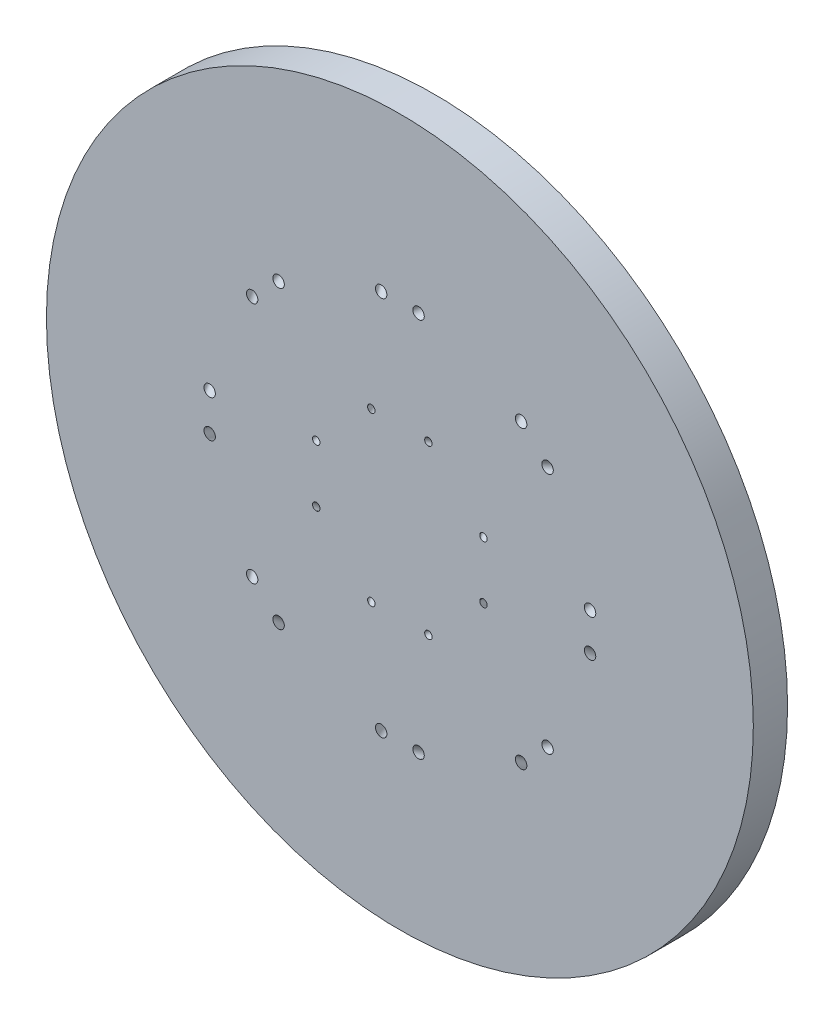
SolidWorks part; units mm, degrees
ref_plane "Front Plane" through (0, 0, 0) normal (0, 0, 1) x (1, 0, 0)
ref_plane "Top Plane" through (0, 0, 0) normal (0, 1, 0) x (1, 0, 0)
ref_plane "Right Plane" through (0, 0, 0) normal (1, 0, 0) x (0, 0, -1)
sketch "Sketch1" plane through (0, 0, 0) normal (0, 0, 1) x (1, 0, 0)
  circle A0 centre (0, 0) radius 38.1
  dimension "D1" = 76.2
extrude "Boss-Extrude1" add sketch "Sketch1" against normal blind 3.6912
sketch "Sketch2" plane through (0, 0, 0) normal (0, 0, 1) x (1, 0, 0)
  line L0 (0, 0) -> (0, 20.6) construction
  line L1 (0, 0) -> (20.6, 0) construction
  circle A0 centre (0, 0) radius 20.6 construction
  circle A1 centre (0, 0) radius 9.525 construction
  dimension "D1" = 41.2
  dimension "D2" = 19.05
sketch "Sketch4" plane through (0, 0, 0) normal (0, 0, 1) x (1, 0, 0)
  line L0 (-3.076, 9.0146) -> (3.076, 9.0146) construction
  line L1 (0, 0) -> (0, 20.6) construction
  line L3 (9.0146, 3.076) -> (9.0146, -3.076) construction
  line L4 (3.076, -9.0146) -> (-3.076, -9.0146) construction
  line L5 (-9.0146, -3.076) -> (-9.0146, 3.076) construction
  line L6 (-3.076, -9.0146) -> (3.076, -9.0146) construction
  line L8 (-9.0146, 3.076) -> (-9.0146, -3.076) construction
  circle A1 centre (9.0146, 3.076) radius 0.403
  circle A3 centre (-3.076, 9.0146) radius 0.403
  circle A4 centre (0, 0) radius 9.525 construction
  circle A5 centre (3.076, 9.0146) radius 0.403
  circle A6 centre (9.0146, -3.076) radius 0.403
  circle A7 centre (3.076, -9.0146) radius 0.403
  circle A8 centre (-3.076, -9.0146) radius 0.403
  circle A9 centre (-9.0146, -3.076) radius 0.403
  circle A10 centre (-9.0146, 3.076) radius 0.403
  point P6 (0, 9.0146)
  point P40 (0, 0)
  dimension "D1" = 0.806
  dimension "D2" = 0.806
  dimension "D3" = 6.152
  dimension "D4" = 4
sketch "Sketch5" plane through (0, 0, 0) normal (0, 0, 1) x (1, 0, 0)
  line L0 (-2.015, 20.5012) -> (2.015, 20.5012) construction
  line L1 (0, 0) -> (0, 20.6) construction
  line L2 (13.0717, 15.9214) -> (15.9214, 13.0717) construction
  line L3 (20.5012, -2.015) -> (20.5012, 2.015) construction
  line L4 (13.0717, -15.9214) -> (15.9214, -13.0717) construction
  line L5 (-2.015, -20.5012) -> (2.015, -20.5012) construction
  line L6 (-15.9214, -13.0717) -> (-13.0717, -15.9214) construction
  line L7 (-20.5012, 2.015) -> (-20.5012, -2.015) construction
  line L8 (-13.0717, 15.9214) -> (-15.9214, 13.0717) construction
  circle A0 centre (-2.015, 20.5012) radius 0.6152
  circle A1 centre (0, 0) radius 20.6 construction
  circle A2 centre (2.015, 20.5012) radius 0.6152
  circle A3 centre (13.0717, 15.9214) radius 0.6152
  circle A4 centre (15.9214, 13.0717) radius 0.6152
  circle A5 centre (20.5012, 2.015) radius 0.6152
  circle A6 centre (20.5012, -2.015) radius 0.6152
  circle A7 centre (15.9214, -13.0717) radius 0.6152
  circle A8 centre (13.0717, -15.9214) radius 0.6152
  circle A9 centre (2.015, -20.5012) radius 0.6152
  circle A10 centre (-2.015, -20.5012) radius 0.6152
  circle A11 centre (-13.0717, -15.9214) radius 0.6152
  circle A12 centre (-15.9214, -13.0717) radius 0.6152
  circle A13 centre (-20.5012, -2.015) radius 0.6152
  circle A14 centre (-20.5012, 2.015) radius 0.6152
  circle A15 centre (-15.9214, 13.0717) radius 0.6152
  circle A16 centre (-13.0717, 15.9214) radius 0.6152
  point P6 (0, 20.5012)
  point P28 (0, 0)
  dimension "D1" = 1.2304
  dimension "D2" = 1.2304
  dimension "D3" = 4.03
  dimension "D4" = 8
ref_plane "Plane1" through (0, 17.9868, 6.725) normal (0, 0.9367, 0.3502) x (1, 0, 0)
ref_plane "Plane2" through (0, 7.909, -2.9571) normal (0, -0.9367, 0.3502) x (1, 0, 0)
ref_plane "Plane3" through (12.7186, 12.7186, 6.725) normal (0.6623, 0.6623, 0.3502) x (0.7071, -0.7071, 0)
ref_plane "Plane4" through (17.9868, 0, 6.725) normal (0.9367, 0, 0.3502) x (0, 1, 0)
ref_plane "Plane5" through (12.7186, -12.7186, 6.725) normal (0.6623, -0.6623, 0.3502) x (0.7071, 0.7071, 0)
ref_plane "Plane7" through (-7.909, 0, -2.9571) normal (0.9367, 0, 0.3502) x (0, -1, 0)
ref_plane "Plane8" through (0, -7.909, -2.9571) normal (0, 0.9367, 0.3502) x (-1, 0, 0)
ref_plane "Plane9" through (0, -7.909, -2.9571) normal (0, 0.9367, 0.3502) x (1, 0, 0)
ref_plane "Plane10" through (-12.7186, -12.7186, 6.725) normal (-0.6623, -0.6623, 0.3502) x (0.7071, -0.7071, 0)
ref_plane "Plane11" through (-7.909, 0, 2.9571) normal (-0.9367, 0, 0.3502) x (0, 1, 0)
ref_plane "Plane12" through (7.909, 0, -2.9571) normal (-0.9367, 0, 0.3502) x (0, -1, 0)
ref_plane "Plane13" through (-12.7186, 12.7186, 6.725) normal (-0.6623, 0.6623, 0.3502) x (-0.7071, -0.7071, 0)
ref_plane "Plane14" through (0, -17.9868, 6.725) normal (0, -0.9367, 0.3502) x (1, 0, 0)
sketch "Sketch6" plane through (12.7186, -12.7186, 6.725) normal (0.6623, -0.6623, 0.3502) x (0.7071, 0.7071, 0)
  line L0 (-2.015, -7.1797) -> (2.015, -7.1797)
  line L1 (0, -7.1797) -> (0, -3.6896) construction
  line L2 (-2.015, -7.1797) -> (0, -3.6896)
  line L3 (0, -3.6896) -> (2.015, -7.1797)
  dimension "D1" = 60
sketch "Sketch7" plane through (17.9868, 0, 6.725) normal (0.9367, 0, 0.3502) x (0, 1, 0)
  line L0 (-2.015, -7.1797) -> (2.015, -7.1797)
  line L1 (0, -7.1797) -> (0, -3.6896) construction
  line L2 (-2.015, -7.1797) -> (0, -3.6896)
  line L3 (0, -3.6896) -> (2.015, -7.1797)
  dimension "D1" = 60
sketch "Sketch8" plane through (12.7186, 12.7186, 6.725) normal (0.6623, 0.6623, 0.3502) x (0.7071, -0.7071, 0)
  line L0 (-2.015, 7.1797) -> (2.015, 7.1797)
  line L1 (0, 7.1797) -> (0, 3.6896) construction
  line L3 (-2.015, 7.1797) -> (0, 3.6896)
  line L4 (0, 3.6896) -> (2.015, 7.1797)
  dimension "D1" = 60
sketch "Sketch9" plane through (0, 17.9868, 6.725) normal (0, 0.9367, 0.3502) x (1, 0, 0)
  line L0 (-2.015, 7.1797) -> (2.015, 7.1797)
  line L1 (0, 7.1797) -> (0, 3.6896) construction
  line L2 (0, 0) -> (0, 7.2143) construction
  line L3 (-2.015, 7.1797) -> (0, 3.6896)
  line L4 (0, 3.6896) -> (2.015, 7.1797)
  dimension "D1" = 60
sketch "Sketch10" plane through (0, 7.909, -2.9571) normal (0, -0.9367, 0.3502) x (1, 0, 0)
  line L0 (-3.076, 3.157) -> (3.076, 3.157)
  line L1 (0, 3.157) -> (0, 8.4848) construction
  line L2 (0, 0) -> (0, 7.2143) construction
  line L3 (0, 8.4848) -> (-3.076, 3.157)
  line L4 (0, 8.4848) -> (3.076, 3.157)
  dimension "D1" = 60
sketch "Sketch12" plane through (-7.909, 0, -2.9571) normal (0.9367, 0, 0.3502) x (0, -1, 0)
  line L0 (-3.076, -3.157) -> (3.076, -3.157)
  line L1 (0, -3.157) -> (0, -8.4848) construction
  line L2 (-3.076, -3.157) -> (0, -8.4848)
  line L3 (0, -8.4848) -> (3.076, -3.157)
  dimension "D1" = 60
sketch "Sketch14" plane through (0, -7.909, -2.9571) normal (0, 0.9367, 0.3502) x (1, 0, 0)
  line L0 (-3.076, -3.157) -> (3.076, -3.157)
  line L1 (0, -3.157) -> (0, -8.4848) construction
  line L2 (-3.076, -3.157) -> (0, -8.4848)
  line L3 (0, -8.4848) -> (3.076, -3.157)
  dimension "D1" = 60
ref_plane "Plane15" through (-17.9868, 0, 6.725) normal (-0.9367, 0, 0.3502) x (0, -1, 0)
sketch "Sketch16" plane through (7.909, 0, -2.9571) normal (-0.9367, 0, 0.3502) x (0, -1, 0)
  line L0 (-3.076, 3.157) -> (3.076, 3.157)
  line L4 (-3.076, 3.157) -> (0, 8.4848)
  line L5 (0, 8.4848) -> (3.076, 3.157)
  line L6 (0, 3.157) -> (0, 8.4848) construction
  dimension "D2" = 60
sketch "Sketch17" plane through (0, -7.909, -2.9571) normal (0, 0.9367, 0.3502) x (-1, 0, 0)
  line L0 (-3.076, 3.157) -> (3.076, 3.157)
  line L1 (0, 3.157) -> (0, 8.4848) construction
  line L3 (-3.076, 3.157) -> (0, 8.4848)
  line L4 (0, 8.4848) -> (3.076, 3.157)
  dimension "D1" = 60
sketch "Sketch18" plane through (0, 17.9868, 6.725) normal (0, 0.9367, 0.3502) x (1, 0, 0)
  line L0 (0, 10.3969) -> (0, -5.2208) construction
sketch "Sketch20" plane through (0, 7.909, -2.9571) normal (0, -0.9367, 0.3502) x (1, 0, 0)
  line L0 (0, 3.157) -> (0, 18.139) construction
sketch "Sketch21" plane through (-12.7186, -12.7186, 6.725) normal (-0.6623, -0.6623, 0.3502) x (0.7071, -0.7071, 0)
  line L0 (-2.015, -7.1797) -> (2.015, -7.1797)
  line L1 (2.015, -7.1797) -> (0, -3.6896)
  line L2 (0, -3.6896) -> (-2.015, -7.1797)
  line L3 (0, -7.1797) -> (0, -3.6896) construction
  dimension "D1" = 60
sketch "Sketch22" plane through (-12.7186, 12.7186, 6.725) normal (-0.6623, 0.6623, 0.3502) x (-0.7071, -0.7071, 0)
  line L0 (2.015, -7.1797) -> (-2.015, -7.1797)
  line L1 (-2.015, -7.1797) -> (0, -3.6896)
  line L2 (0, -3.6896) -> (2.015, -7.1797)
  line L3 (0, -7.1797) -> (0, -3.6896) construction
  dimension "D1" = 60
sketch "Sketch23" plane through (0, -17.9868, 6.725) normal (0, -0.9367, 0.3502) x (1, 0, 0)
  line L0 (-2.015, -7.1797) -> (2.015, -7.1797)
  line L1 (2.015, -7.1797) -> (0, -3.6896)
  line L2 (0, -3.6896) -> (-2.015, -7.1797)
  line L3 (0, -3.6896) -> (0, -7.1797) construction
  dimension "D1" = 60
sketch "Sketch24" plane through (-17.9868, 0, 6.725) normal (-0.9367, 0, 0.3502) x (0, -1, 0)
  line L0 (-2.015, -7.1797) -> (2.015, -7.1797)
  line L1 (2.015, -7.1797) -> (0, -3.6896)
  line L2 (0, -3.6896) -> (-2.015, -7.1797)
  line L3 (0, -3.6896) -> (0, -7.1797) construction
  dimension "D1" = 60
extrude "Cut-Extrude1" cut sketch "Sketch5" along direction (0.5, -0.3033, 0.8112) on the side against the normal up to surface (3.6912 mm away) contours A0 up to face at (38.1, 0, -3.6912)
extrude "Cut-Extrude2" cut sketch "Sketch5<3>" along direction (0.5, 0.3033, -0.8112) on the side against the normal up to surface (3.6912 mm away) contours A2 region at (2.015, 20.5012, 0) up to face at (-4.9032, 21.8293, -3.6912)
sketch "Sketch5<3>" plane through (0, 0, 0) normal (0, 0, 1) x (1, 0, 0) same geometry as "Sketch5"
extrude "Cut-Extrude3" cut sketch "Sketch5<4>" along direction (0.1391, -0.568, 0.8112) on the side against the normal up to surface (3.6912 mm away) contours A3 region at (13.0717, 15.9214, 0) up to face at (3.6772, 21.8293, -3.6912)
sketch "Sketch5<4>" plane through (0, 0, 0) normal (0, 0, 1) x (1, 0, 0) same geometry as "Sketch5"
extrude "Cut-Extrude4" cut sketch "Sketch5<5>" along direction (0.568, -0.1391, -0.8112) on the side against the normal up to surface (3.6912 mm away) contours A4 region at (15.9214, 13.0717, 0) up to face at (11.8258, 18.454, -3.6912)
sketch "Sketch5<5>" plane through (0, 0, 0) normal (0, 0, 1) x (1, 0, 0) same geometry as "Sketch5"
extrude "Cut-Extrude5" cut sketch "Sketch5<6>" along direction (-0.3033, 0.5, 0.8112) on the side against the normal up to surface (3.6912 mm away) contours A6 region at (20.5012, -2.015, 0) up to face at (17.893, 12.3868, -3.6912)
sketch "Sketch5<6>" plane through (0, 0, 0) normal (0, 0, 1) x (1, 0, 0) same geometry as "Sketch5"
extrude "Cut-Extrude6" cut sketch "Sketch5<7>" along direction (0.3033, 0.5, -0.8112) on the side against the normal up to surface (3.6912 mm away) contours A5 region at (20.5012, 2.015, 0) up to face at (21.2683, -4.3422, -3.6912)
sketch "Sketch5<7>" plane through (0, 0, 0) normal (0, 0, 1) x (1, 0, 0) same geometry as "Sketch5"
extrude "Cut-Extrude7" cut sketch "Sketch5<8>" along direction (0.1391, 0.568, 0.8112) on the side against the normal up to surface (3.6912 mm away) contours A8 region at (13.0717, -15.9214, 0) up to face at (21.2683, 4.2382, -3.6912)
sketch "Sketch5<8>" plane through (0, 0, 0) normal (0, 0, 1) x (1, 0, 0) same geometry as "Sketch5"
extrude "Cut-Extrude8" cut sketch "Sketch5<9>" along direction (0.568, 0.1391, -0.8112) on the side against the normal up to surface (3.6912 mm away) contours A7 region at (15.9214, -13.0717, 0) up to face at (11.8258, -18.5581, -3.6912)
sketch "Sketch5<9>" plane through (0, 0, 0) normal (0, 0, 1) x (1, 0, 0) same geometry as "Sketch5"
extrude "Cut-Extrude9" cut sketch "Sketch4" along direction (-0.5, -0.3033, -0.8112) on the side against the normal up to surface (3.6912 mm away) contours A3 region at (-3.076, 9.0146, 0) up to face at (17.893, -12.4908, -3.6912)
extrude "Cut-Extrude10" cut sketch "Sketch4<3>" along direction (0.5, -0.3033, -0.8112) on the side against the normal up to surface (3.6912 mm away) contours A5 region at (3.076, 9.0146, 0) up to face at (-5.7528, 7.6005, -3.6912)
sketch "Sketch4<3>" plane through (0, 0, 0) normal (0, 0, 1) x (1, 0, 0) same geometry as "Sketch4"
extrude "Cut-Extrude11" cut sketch "Sketch4<4>" along direction (0.5, -0.3033, 0.8112) on the side against the normal up to surface (3.6912 mm away) contours A8 region at (-3.076, -9.0146, 0) up to face at (4.9496, 7.6005, -3.6912)
sketch "Sketch4<4>" plane through (0, 0, 0) normal (0, 0, 1) x (1, 0, 0) same geometry as "Sketch4"
extrude "Cut-Extrude12" cut sketch "Sketch4<6>" along direction (0.5, 0.3033, -0.8112) on the side against the normal up to surface (3.6912 mm away) contours A7 region at (3.076, -9.0146, 0) up to face at (-5.7528, -7.6686, -3.6912)
sketch "Sketch4<6>" plane through (0, 0, 0) normal (0, 0, 1) x (1, 0, 0) same geometry as "Sketch4"
extrude "Cut-Extrude13" cut sketch "Sketch4<7>" along direction (-0.3033, -0.5, 0.8112) on the side against the normal up to surface (3.6912 mm away) contours A10 region at (-9.0146, 3.076, 0) up to face at (4.9496, -7.6686, -3.6912)
sketch "Sketch4<7>" plane through (0, 0, 0) normal (0, 0, 1) x (1, 0, 0) same geometry as "Sketch4"
extrude "Cut-Extrude14" cut sketch "Sketch4<8>" along direction (0.3033, -0.5, -0.8112) on the side against the normal up to surface (3.6912 mm away) contours A9 region at (-9.0146, -3.076, 0) up to face at (-8.0361, 5.3171, -3.6912)
sketch "Sketch4<8>" plane through (0, 0, 0) normal (0, 0, 1) x (1, 0, 0) same geometry as "Sketch4"
extrude "Cut-Extrude26" cut sketch "Sketch5<10>" along direction (-0.5, 0.3033, 0.8112) on the side against the normal up to surface (3.6912 mm away) contours A9 region at (2.015, -20.5012, 0) up to face at (-8.0361, -5.3853, -3.6912)
sketch "Sketch5<10>" plane through (0, 0, 0) normal (0, 0, 1) x (1, 0, 0) same geometry as "Sketch5"
extrude "Cut-Extrude27" cut sketch "Sketch5<11>" along direction (-0.5, -0.3033, -0.8112) on the side against the normal up to surface (3.6912 mm away) contours A10 region at (-2.015, -20.5012, 0) up to face at (3.6772, -21.9333, -3.6912)
sketch "Sketch5<11>" plane through (0, 0, 0) normal (0, 0, 1) x (1, 0, 0) same geometry as "Sketch5"
extrude "Cut-Extrude28" cut sketch "Sketch5<12>" along direction (-0.1391, 0.568, 0.8112) on the side against the normal up to surface (3.6912 mm away) contours A11 region at (-13.0717, -15.9214, 0) up to face at (-4.9032, -21.9333, -3.6912)
sketch "Sketch5<12>" plane through (0, 0, 0) normal (0, 0, 1) x (1, 0, 0) same geometry as "Sketch5"
extrude "Cut-Extrude29" cut sketch "Sketch5<13>" along direction (-0.568, 0.1391, -0.8112) on the side against the normal up to surface (3.6912 mm away) contours A12 region at (-15.9214, -13.0717, 0) up to face at (-13.0518, -18.5581, -3.6912)
sketch "Sketch5<13>" plane through (0, 0, 0) normal (0, 0, 1) x (1, 0, 0) same geometry as "Sketch5"
extrude "Cut-Extrude30" cut sketch "Sketch5<14>" along direction (0.3033, 0.5, 0.8112) on the side against the normal up to surface (3.6912 mm away) contours A13 region at (-20.5012, -2.015, 0) up to face at (-19.119, -12.4908, -3.6912)
sketch "Sketch5<14>" plane through (0, 0, 0) normal (0, 0, 1) x (1, 0, 0) same geometry as "Sketch5"
extrude "Cut-Extrude31" cut sketch "Sketch5<15>" along direction (-0.3033, 0.5, -0.8112) on the side against the normal up to surface (3.6912 mm away) contours A14 region at (-20.5012, 2.015, 0) up to face at (-22.4943, -4.3422, -3.6912)
sketch "Sketch5<15>" plane through (0, 0, 0) normal (0, 0, 1) x (1, 0, 0) same geometry as "Sketch5"
extrude "Cut-Extrude32" cut sketch "Sketch5<16>" along direction (-0.568, -0.1391, -0.8112) on the side against the normal up to surface (3.6912 mm away) contours A15 region at (-15.9214, 13.0717, 0) up to face at (-22.4943, 4.2382, -3.6912)
sketch "Sketch5<16>" plane through (0, 0, 0) normal (0, 0, 1) x (1, 0, 0) same geometry as "Sketch5"
extrude "Cut-Extrude33" cut sketch "Sketch5<17>" along direction (-0.1391, -0.568, 0.8112) on the side against the normal up to surface (3.6912 mm away) contours A16 region at (-13.0717, 15.9214, 0) up to face at (-19.119, 12.3868, -3.6912)
sketch "Sketch5<17>" plane through (0, 0, 0) normal (0, 0, 1) x (1, 0, 0) same geometry as "Sketch5"
extrude "Cut-Extrude34" cut sketch "Sketch4<20>" along direction (-0.3033, -0.5, -0.8112) on the side against the normal up to surface (3.6912 mm away) contours A6 region at (9.0146, -3.076, 0) up to face at (-13.0518, 18.454, -3.6912)
sketch "Sketch4<20>" plane through (0, 0, 0) normal (0, 0, 1) x (1, 0, 0) same geometry as "Sketch4"
extrude "Cut-Extrude35" cut sketch "Sketch4<21>" along direction (0.3033, -0.5, 0.8112) on the side against the normal up to surface (3.6912 mm away) contours A1 region at (9.0146, 3.076, 0) up to face at (7.233, -5.3853, -3.6912)
sketch "Sketch4<21>" plane through (0, 0, 0) normal (0, 0, 1) x (1, 0, 0) same geometry as "Sketch4"
sketch "Sketch25" plane through (0, 0, -3.6912) normal (0, 0, -1) x (-1, 0, 0)
  line L0 (5.3512, 8.0376) -> (5.3512, 7.2316)
  line L1 (3.9163, 5.5874) -> (6.7861, 9.6818)
  line L2 (16.0162, 10.7653) -> (18.506, 12.4388)
  line L5 (18.506, 12.4388) -> (20.9959, 14.1123)
  line L6 (19.1212, 12.4388) -> (17.8908, 12.4388)
  line L7 (0, 0) -> (16.0162, 10.7653) construction
  line L8 (0, 0) -> (3.9163, 5.5874) construction
  circle A0 centre (0, 0) radius 11.8232 construction
  circle A1 centre (0, 0) radius 19.2979 construction
  circle A2 centre (0, 0) radius 6.8232
  circle A3 centre (5.3512, 7.6346) radius 0.403 construction
  circle A6 centre (0, 0) radius 25.2979 construction
  circle A9 centre (18.506, 12.4388) radius 0.6152 construction
  point P10 (5.3512, 7.6346)
  point P12 (0, 0)
  point P13 (0, 0)
  point P24 (18.506, 12.4388)
  point P25 (0, 0)
  point P26 (5.3512, 7.6346)
  dimension "D1" = 5
  dimension "D2" = 6
  dimension "D3" = 38.5958
  dimension "D4" = 13.6464
  dimension "D5" = 23.6464
  dimension "D6" = 50.5958
equation "\"PLATE DIAMETER\"= 0.0762"
equation "\"FUEL ORIFICE DIAMETER\"= 0.000805996"
equation "\"OXIDIZER ORIFICE DIAMETER\"= 0.0012304"
equation "\"IMPINGE ANGLE\"= 60"
equation "\"FUEL ORIFICE LENGTH\"= 0.00241799"
equation "\"OXIDIZER ORIFICE LENGTH\"= 0.0036912"
equation "\"FUEL JET LENGTH\"= 0.00402998"
equation "\"OXIDIZER JET LENGTH\"= 0.006152"
equation "\"D1@Sketch1\"=\"PLATE DIAMETER\""
equation "\"D1@Boss-Extrude1\"=\"OXIDIZER ORIFICE LENGTH\""
equation "\"D1@Sketch2\"=\"PLATE DIAMETER\"-0.035"
equation "\"D2@Sketch2\"=\"PLATE DIAMETER\"/4"
equation "\"D1@Sketch4\"=\"FUEL ORIFICE DIAMETER\""
equation "\"D2@Sketch4\"=\"FUEL ORIFICE DIAMETER\""
equation "\"D3@Sketch4\"=\"OXIDIZER JET LENGTH\""
equation "\"D1@Sketch5\"=\"OXIDIZER ORIFICE DIAMETER\""
equation "\"D2@Sketch5\"=\"OXIDIZER ORIFICE DIAMETER\""
equation "\"D3@Sketch5\"=\"FUEL JET LENGTH\""
equation "\"D1@Sketch6\"=\"IMPINGE ANGLE\""
equation "\"D1@Sketch7\"=\"IMPINGE ANGLE\""
equation "\"D1@Sketch8\"=\"IMPINGE ANGLE\""
equation "\"D1@Sketch9\"=\"IMPINGE ANGLE\""
equation "\"D1@Sketch10\"=\"IMPINGE ANGLE\""
equation "\"D1@Sketch12\"=\"IMPINGE ANGLE\""
equation "\"D1@Sketch14\"=\"IMPINGE ANGLE\""
equation "\"D1@Sketch17\"=\"IMPINGE ANGLE\""
equation "\"D2@Sketch16\"=\"IMPINGE ANGLE\""
equation "\"D1@Sketch21\"=\"IMPINGE ANGLE\""
equation "\"D1@Sketch22\"=\"IMPINGE ANGLE\""
equation "\"D1@Sketch23\"=\"IMPINGE ANGLE\""
equation "\"D1@Sketch24\"=\"IMPINGE ANGLE\""
